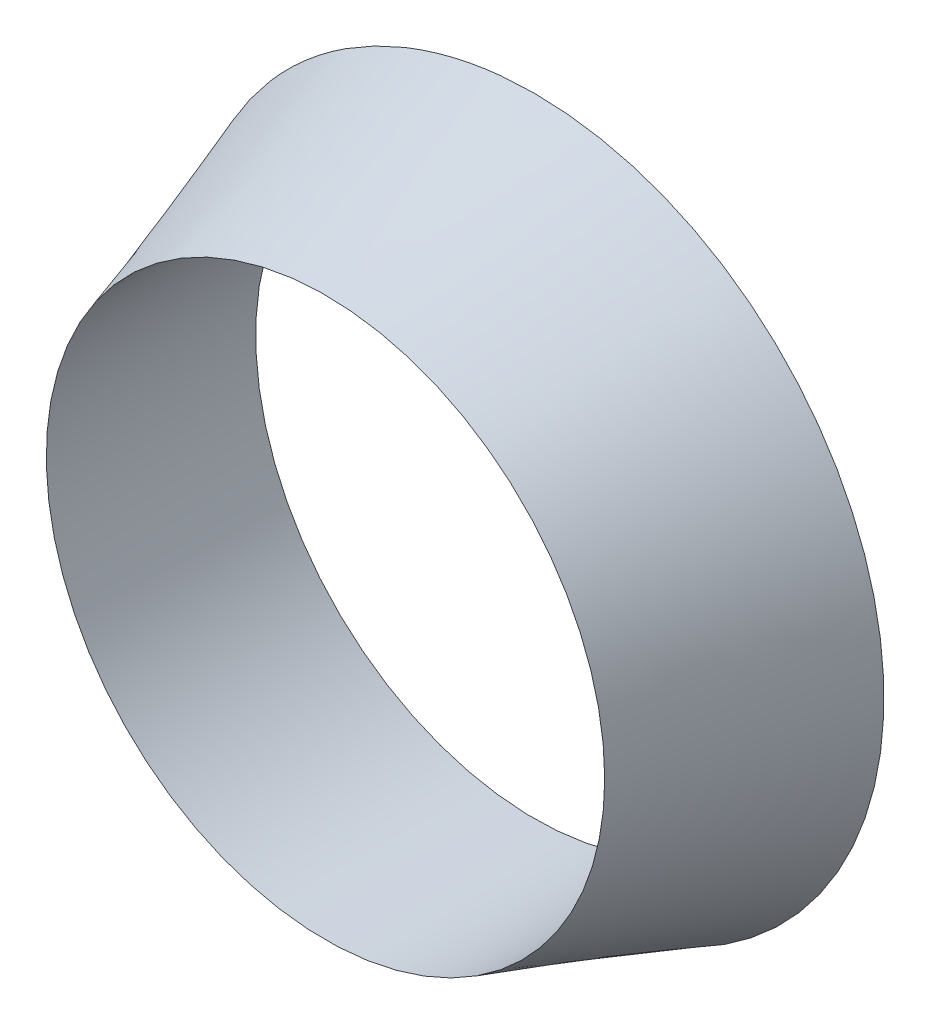
SolidWorks part; units mm, degrees
ref_plane "Front Plane" through (0, 0, 0) normal (0, 0, 1) x (1, 0, 0)
ref_plane "Top Plane" through (0, 0, 0) normal (0, 1, 0) x (1, 0, 0)
ref_plane "Right Plane" through (0, 0, 0) normal (1, 0, 0) x (0, 0, -1)
sketch "Sketch2" plane through (0, 0, 0) normal (0, 0, 1) x (1, 0, 0)
  circle A0 centre (0, 0) radius 4
ref_plane "Plane1" through (0, 0, -3) normal (0, 0, 1) x (1, 0, 0)
sketch "Sketch3" plane through (0, 0, -3) normal (0, 0, 1) x (1, 0, 0)
  circle A0 centre (0, 0) radius 5
loft "Loft1" add profiles "Sketch2", "Sketch3" connector at (2.5108, -3.1138, 0) connector at (2.3007, -4.4392, -3)
sketch "Sketch4" plane through (0, 0, 0) normal (0, 0, 1) x (1, 0, 0)
  circle A0 centre (0, 0) radius 4
extrude "Cut-Extrude1" cut sketch "Sketch4" against normal blind 10
